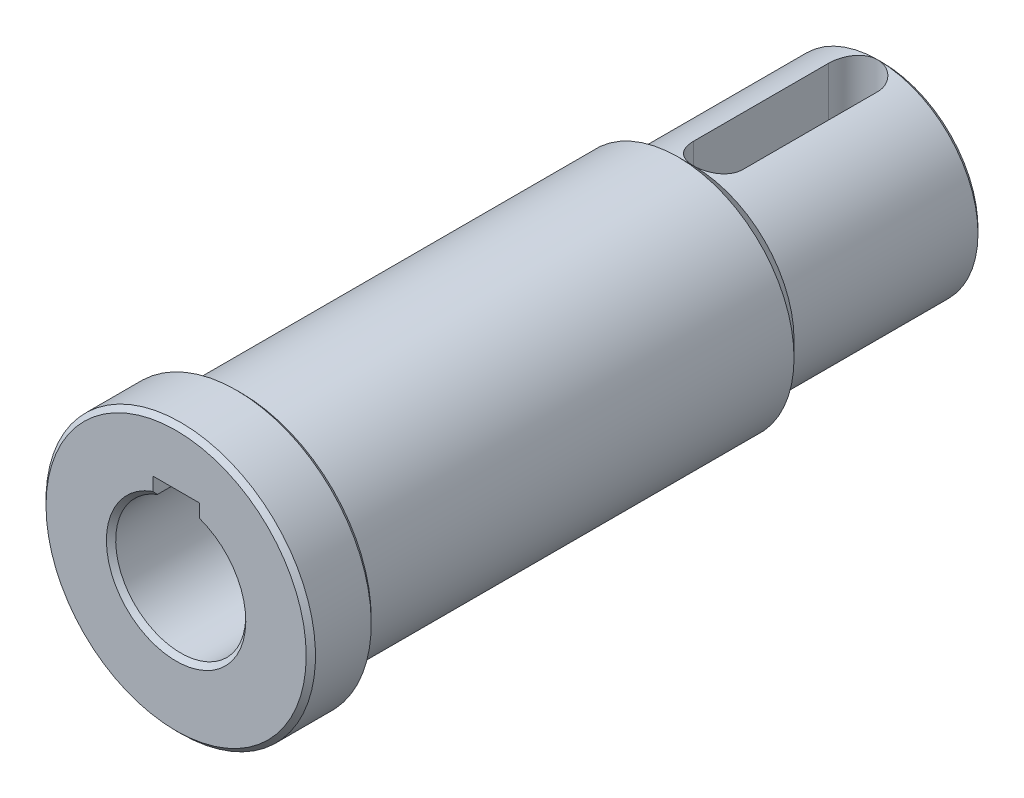
SolidWorks part; units mm, degrees
ref_plane "前视基准面" through (0, 0, 0) normal (0, 0, 1) x (1, 0, 0)
ref_plane "上视基准面" through (0, 0, 0) normal (0, 1, 0) x (1, 0, 0)
ref_plane "右视基准面" through (0, 0, 0) normal (1, 0, 0) x (0, 0, -1)
other "Configuration Table"
sketch "草图1" plane through (0, 0, 0) normal (1, 0, 0) x (0, 0, -1)
  line L0 (0, 0) -> (0, 14.5)
  line L1 (0, 14.5) -> (7, 14.5)
  line L2 (7, 14.5) -> (7, 12.5)
  line L3 (7, 12.5) -> (56, 12.5)
  line L4 (56, 12.5) -> (56, 10.7958)
  line L5 (56, 10.7958) -> (76, 10.7958)
  line L6 (76, 10.7958) -> (76, 0)
  line L7 (76, 0) -> (0, 0)
  dimension "D1" = 14.5
  dimension "D2" = 12.5
  dimension "D3" = 10.7958
  dimension "D4" = 49
  dimension "D5" = 56
  dimension "D6" = 20
revolve "旋转1" add sketch "草图1" angle 360 about L7
sketch "草图3" plane through (0, 0, 0) normal (1, 0, 0) x (0, 0, -1)
  line L0 (0, 0) -> (0, 7)
  line L1 (0, 14.5) -> (0, -14.5) construction
  line L2 (0, 7) -> (33.5, 7)
  line L3 (33.5, 7) -> (33.5, 2.75)
  line L4 (33.5, 2.75) -> (76, 2.75)
  line L5 (76, -10.7958) -> (76, 10.7958) construction
  line L6 (76, 2.75) -> (76, 0)
  line L7 (76, 0) -> (0, 0)
  dimension "D1" = 7
  dimension "D2" = 2.75
  dimension "D3" = 33.5
revolve "切除-旋转1" cut sketch "草图3" angle 360 about L7
fillet "圆角1" radius 1 1 edges at (0, 7, -33.5)
chamfer "倒角1" distance 0.5 angle 45 6 edges at (0, 2.75, -76) (0, 10.7958, -76) (0, 14.5, 0) (0, 7, 0) (0, 14.5, -7) (0, 2.75, -33.5)
chamfer "倒角2" distance 2 angle 45 1 edges at (0, 12.5, -56)
sketch "草图4" plane through (0, 0, 0) normal (0, 0, 1) x (1, 0, 0)
  line L1 (-2.5, 8.5) -> (2.5, 8.5)
  line L2 (-2.5, 8.5) -> (-2.5, 0)
  line L3 (-2.5, 0) -> (2.5, 0)
  line L4 (2.5, 8.5) -> (2.5, 0)
  line L5 (-2.5, 8.5) -> (2.5, 0) construction
  line L6 (-2.5, 0) -> (2.5, 8.5) construction
  circle A1 centre (0, 0) radius 7.5 construction
  point P0 (0, 4.25)
  dimension "D1" = 5
  dimension "D2" = 16
extrude "切除-拉伸1" cut sketch "草图4" against normal blind 30
ref_plane "基准面1" through (0, 4.5, 0) normal (0, 1, 0) x (1, 0, 0)
sketch "草图5" plane through (0, 4.5, 0) normal (0, 1, 0) x (1, 0, 0)
  line L0 (0, 72.8521) -> (0, 58.3521) construction
  line L1 (2.6479, 72.8521) -> (2.6479, 58.3521)
  line L2 (-2.6479, 72.8521) -> (-2.6479, 58.3521)
  line L3 (-10.7958, 75.5) -> (10.7958, 75.5) construction
  line L4 (-10.7958, 55.7042) -> (10.7958, 55.7042) construction
  arc A0 (2.6479, 72.8521) -> (-2.6479, 72.8521) centre (0, 72.8521) ccw
  arc A1 (-2.6479, 58.3521) -> (2.6479, 58.3521) centre (0, 58.3521) ccw
  point P2 (0, 65.6021)
  dimension "D1" = 14.5
extrude "切除-拉伸2" cut sketch "草图5" along normal through all
